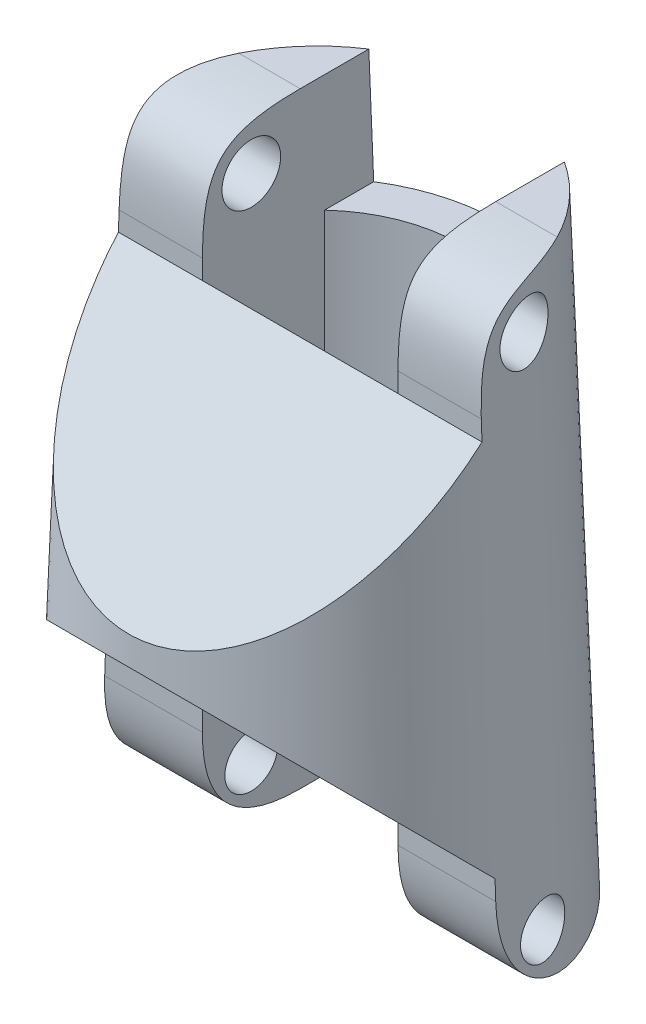
SolidWorks part; units mm, degrees
ref_plane "Front Plane" through (0, 0, 0) normal (0, 0, 1) x (1, 0, 0)
ref_plane "Top Plane" through (0, 0, 0) normal (0, 1, 0) x (1, 0, 0)
ref_plane "Right Plane" through (0, 0, 0) normal (1, 0, 0) x (0, 0, -1)
sketch "Sketch1" plane through (0, 0, 0) normal (0, 1, 0) x (1, 0, 0)
  circle A0 centre (0, 0) radius 10
  dimension "D1" = 20
extrude "Boss-Extrude1" add sketch "Sketch1" along normal blind 25 draft 2 and the other way blind 6 draft 2
sketch "Sketch2" plane through (0, 0, 0) normal (1, 0, 0) x (0, 0, -1)
  line L0 (-0.873, 25) -> (-0.873, 19)
  line L2 (9.127, 25) -> (-9.127, 25) construction
  line L3 (-0.873, 19) -> (-12.8981, 6.9749)
  line L5 (-12.8981, 6.9749) -> (-12.8981, 25)
  line L6 (-12.8981, 25) -> (-0.873, 25)
  dimension "D1" = 10
  dimension "D2" = 6
  dimension "D3" = 135
extrude "Cut-Extrude1" cut sketch "Sketch2" against normal through all both and the other way through all
sketch "Sketch3" plane through (0, 0, 0.873) normal (0, 0, 1) x (1, 0, 0)
  line L0 (-9.2956, 19) -> (9.2956, 19) construction
  line L1 (5, 25) -> (-5, 25)
  line L2 (5, 25) -> (5, 19)
  line L3 (5, 19) -> (-5, 19)
  line L4 (-5, 25) -> (-5, 19)
  line L5 (5, 25) -> (-5, 19) construction
  line L6 (5, 19) -> (-5, 25) construction
  point P0 (0, 22)
  dimension "D1" = 10
  dimension "D2" = 6
extrude "Cut-Extrude2" cut sketch "Sketch3" against normal blind 25
sketch "Sketch4" plane through (-5, 0, 0) normal (1, 0, 0) x (0, 0, -1)
  circle A0 centre (1.627, 22.5) radius 1.5
  dimension "D3" = 3
  dimension "D1" = 2.5
  dimension "D2" = 2.5
extrude "Cut-Extrude3" cut sketch "Sketch4" against normal through all both and the other way through all
fillet "Fillet2" radius 5 2 edges at (7.0426, 25, 0.873) (-7.0426, 25, 0.873)
sketch "Sketch7" plane through (0, 0, 0) normal (1, 0, 0) x (0, 0, -1)
  line L0 (-0.873, -6) -> (-0.873, 0)
  line L1 (-10.2095, -6) -> (10.2095, -6) construction
  line L2 (-0.873, 0) -> (-11.3178, 10.4448)
  line L3 (-11.3178, 10.4448) -> (-11.3178, -6)
  line L4 (-11.3178, -6) -> (-0.873, -6)
  dimension "D1" = 6
  dimension "D2" = 135
extrude "Cut-Extrude5" cut sketch "Sketch7" against normal through all both and the other way through all
sketch "Sketch8" plane through (0, 0, 0.873) normal (0, 0, 1) x (1, 0, 0)
  line L0 (-9.9618, 0) -> (9.9618, 0) construction
  line L1 (-5, -6) -> (5, -6)
  line L2 (-5, -6) -> (-5, 0)
  line L3 (-5, 0) -> (5, 0)
  line L4 (5, -6) -> (5, 0)
  line L5 (-5, -6) -> (5, 0) construction
  line L6 (-5, 0) -> (5, -6) construction
  point P0 (0, -3)
  dimension "D1" = 6
  dimension "D2" = 10
  dimension "D3" = 0
extrude "Cut-Extrude6" cut sketch "Sketch8" against normal through all
sketch "Sketch6" plane through (0, 19, 0) normal (0, 1, 0) x (1, 0, 0)
  line L0 (5, 7.8848) -> (5, -0.873) construction
  line L1 (-5, -0.873) -> (5, -0.873) construction
  line L2 (-5, 7.8848) -> (-5, -0.873) construction
  line L3 (5, 5.3688) -> (5, -0.873)
  line L4 (-5, -0.873) -> (5, -0.873)
  line L5 (-5, 5.3688) -> (-5, -0.873)
  arc A3 (3.9289, 6.1958) -> (-3.9289, 6.1958) centre (0, 0) ccw
  arc A4 (5, 5.3688) -> (-5, 5.3688) centre (0, 0) ccw
  dimension "D1" = 2
extrude "Cut-Extrude7" cut sketch "Sketch6" against normal through all contours A4 L5 L4 L3
sketch "Sketch9" plane through (-5, 0, 0) normal (1, 0, 0) x (0, 0, -1)
  circle A0 centre (1.627, -3.5) radius 1.3515
  dimension "D1" = 2.5
  dimension "D2" = 2.5
extrude "Cut-Extrude8" cut sketch "Sketch9" against normal through all both and the other way through all
fillet "Fillet3" radius 5 2 edges at (7.5861, -6, 0.873) (-7.5861, -6, 0.873)
